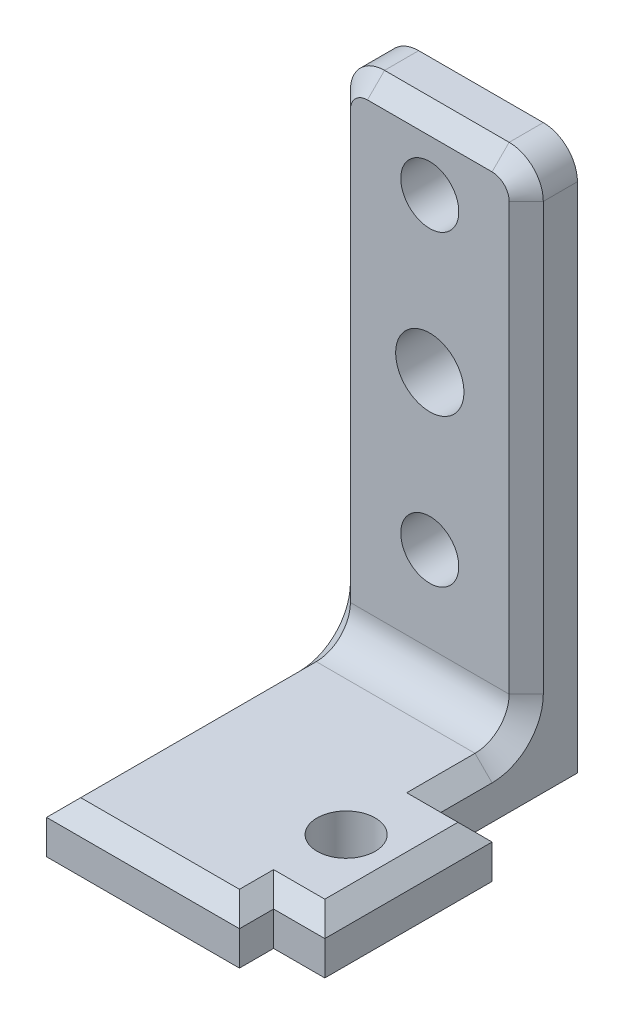
SolidWorks part; units mm, degrees
material "6061-T6 (SS)"
ref_plane "Front Plane" through (0, 0, 0) normal (0, 0, 1) x (1, 0, 0)
ref_plane "Top Plane" through (0, 0, 0) normal (0, 1, 0) x (1, 0, 0)
ref_plane "Right Plane" through (0, 0, 0) normal (1, 0, 0) x (0, 0, -1)
ref_axis "Axis1" through (0, 0, 55) along (0, 0, -1)
sketch "Sketch1" plane through (0, 0, 0) normal (0, 1, 0) x (1, 0, 0)
  line L1 (-5.65, 9.9) -> (5.65, 9.9)
  line L2 (-5.65, 9.9) -> (-5.65, -9.9)
  line L3 (-5.65, -9.9) -> (5.65, -9.9)
  line L4 (5.65, 9.9) -> (5.65, -9.9)
  line L5 (-5.65, 9.9) -> (5.65, -9.9) construction
  line L6 (-5.65, -9.9) -> (5.65, 9.9) construction
  line L7 (5.65, 1.9) -> (8.65, 1.9)
  line L8 (5.65, 1.9) -> (5.65, -7.9)
  line L9 (5.65, -7.9) -> (8.65, -7.9)
  line L10 (8.65, 1.9) -> (8.65, -7.9)
  line L11 (5.65, 1.9) -> (8.65, -7.9) construction
  line L12 (5.65, -7.9) -> (8.65, 1.9) construction
  circle A0 centre (5, -3) radius 1.7
  point P0 (0, 0)
  point P12 (7.15, -3)
  point P13 (0, 0)
  point P14 (0, 0)
  point P15 (9.553, -0.3936)
  point P16 (5.65, -0.731)
  dimension "D4" = 3.4
  dimension "D1" = 11.3
  dimension "D2" = 6.9
  dimension "D3" = 12.9
  dimension "D5" = 5
  dimension "D6" = 3
  dimension "D7" = 9.8
extrude "Boss-Extrude1" add sketch "Sketch1" along normal blind 3 contours A0 L4 L1 L2 L3 | A0 L4 L9 L10 L7 region at (-0.1423, 0, -0.0925) region at (7.2441, 0, 3)
sketch "Sketch2" plane through (0, 3, 0) normal (0, 1, 0) x (1, 0, 0)
  line L1 (-5.65, 9.9) -> (5.65, 9.9)
  line L2 (-5.65, 9.9) -> (-5.65, 6.9)
  line L3 (-5.65, 6.9) -> (5.65, 6.9)
  line L4 (5.65, 9.9) -> (5.65, 6.9)
  line L5 (-5.65, 9.9) -> (5.65, 6.9) construction
  line L6 (-5.65, 6.9) -> (5.65, 9.9) construction
  line L7 (5.65, 9.9) -> (5.65, 1.9) construction
  point P4 (0, 8.4)
  point P6 (5.65, 6.9)
  point P8 (5.65, 6.9)
  point P10 (0, 0)
  point P11 (0, 0)
  point P12 (-5.65, 9.9)
  point P14 (5.65, 6.9)
  point P15 (0, 0)
  dimension "D1" = 3
extrude "Boss-Extrude2" add sketch "Sketch2" along normal blind 29
sketch "Sketch3" plane through (0, 0, -9.9) normal (0, 0, -1) x (-1, 0, 0)
  line L0 (0, 28) -> (0, 10) construction
  line L1 (4, 28) -> (4, 10) construction
  line L2 (-4, 28) -> (-4, 10) construction
  line L3 (-5.65, 32) -> (5.65, 32) construction
  arc A0 (4, 28) -> (-4, 28) centre (0, 28) ccw construction
  arc A1 (-4, 10) -> (4, 10) centre (0, 10) ccw construction
  circle A2 centre (0, 28) radius 1.7
  circle A3 centre (0, 10) radius 1.7
  circle A4 centre (0, 19) radius 2
  point P3 (0, 19)
  dimension "D1" = 4
  dimension "D3" = 3.4
  dimension "D4" = 4
  dimension "D2" = 18
extrude "Cut-Extrude1" cut sketch "Sketch3" against normal up to surface (3 mm away) up to face at (0, 17.5, -6.9)
fillet "Fillet1" radius 2 3 edges at (5.65, 32, -8.4) (-5.65, 32, -8.4) (0, 3, -6.9)
chamfer "Chamfer1" distance 1 angle 45 14 edges at (5.65, 17.5, -6.9) (5.0642, 31.4142, -6.9) (0, 32, -6.9) (-5.0642, 31.4142, -6.9) (-5.65, 17.5, -6.9) (5.65, 3, -3.4) (5.65, 3.5858, -6.3142) (-5.65, 3.5858, -6.3142) (7.15, 3, -1.9) (8.65, 3, 3) (7.15, 3, 7.9) (5.65, 3, 8.9) (0, 3, 9.9) (-5.65, 3, 2.5)
equation "\"D1@Sketch1\"=11.500mm-2*.1"
